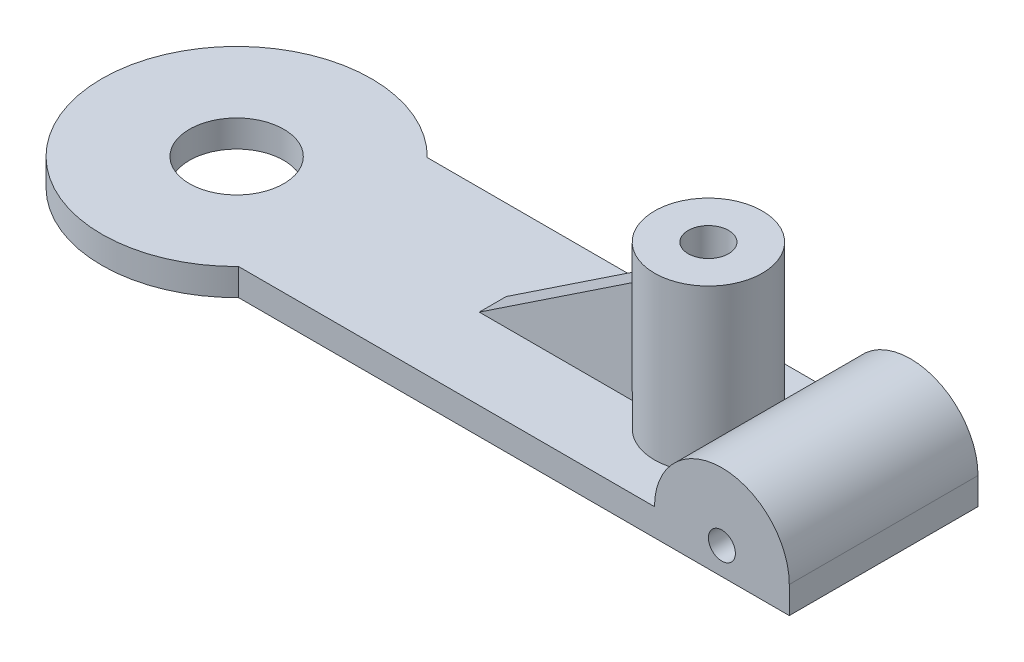
SolidWorks part; units mm, degrees
ref_plane "Front Plane" through (0, 0, 0) normal (0, 0, 1) x (1, 0, 0)
ref_plane "Top Plane" through (0, 0, 0) normal (0, 1, 0) x (1, 0, 0)
ref_plane "Right Plane" through (0, 0, 0) normal (1, 0, 0) x (0, 0, -1)
sketch "Sketch2" plane through (0, 0, 0) normal (0, 1, 0) x (1, 0, 0)
  line L1 (0, -35) -> (-204.2929, -35)
  line L2 (0, -35) -> (0, 35)
  line L3 (0, 35) -> (-204.2929, 35)
  line L5 (0, -35) -> (-204.2929, 35) construction
  line L6 (0, 35) -> (-204.2929, -35) construction
  arc A0 (-204.2929, 35) -> (-204.2929, -35) centre (-240, 0) ccw
  circle A1 centre (-240, 0) radius 17.5
  point P2 (-102.1464, 0)
  point P9 (0, 0)
  point P10 (-37.2613, 35)
  dimension "D1" = 100
  dimension "D2" = 240
  dimension "D3" = 35
  dimension "D4" = 70
extrude "Boss-Extrude1" add sketch "Sketch2" along normal blind 10
sketch "Sketch3" plane through (0, 10, 0) normal (0, 1, 0) x (1, 0, 0)
  circle A0 centre (-65, 0) radius 20
  circle A1 centre (-65, 0) radius 7.5
  point P3 (0, 0)
  dimension "D1" = 40
  dimension "D2" = 15
  dimension "D3" = 65
extrude "Boss-Extrude2" add sketch "Sketch3" along normal blind 60
sketch "Sketch4" plane through (0, 0, 0) normal (0, 0, 1) x (1, 0, 0)
  line L0 (-81.0558, 52.6295) -> (-145, 10)
  line L2 (-204.2929, 10) -> (0, 10) construction
  line L3 (-145, 10) -> (-81.0558, 10)
  line L4 (-81.0558, 10) -> (-81.0558, 52.6295)
  line L6 (-145, 10) -> (-81.0558, 10)
  line L7 (-50, 10) -> (0, 10)
  line L8 (-85, 70) -> (-85, 10) construction
  line L9 (-45, 70) -> (-85, 70) construction
  arc A0 (0, 10) -> (-50, 10) centre (-25, 10) ccw
  point P6 (-85, 50)
  dimension "D3" = 25
  dimension "D1" = 20
  dimension "D2" = 145
  dimension "D4" = 42.6295
extrude "Boss-Extrude7" add sketch "Sketch4" along normal mid plane 10 contours L3 L4 L0 region at (-102.3705, 24.2098, 0)
extrude "Boss-Extrude8" add sketch "Sketch4<6>" along normal mid plane 70 contours L7 A0 region at (-25, 20.6103, 0)
sketch "Sketch4<6>" plane through (0, 0, 0) normal (0, 0, 1) x (1, 0, 0) same geometry as "Sketch4"
sketch "Sketch5" plane through (0, 0, 35) normal (0, 0, 1) x (1, 0, 0)
  circle A0 centre (-25, 10) radius 5
  arc A1 (0, 10) -> (-50, 10) centre (-25, 10) ccw construction
  point P2 (-25.5997, 16.8018)
  dimension "D1" = 10
extrude "Cut-Extrude1" cut sketch "Sketch5" against normal blind 70
